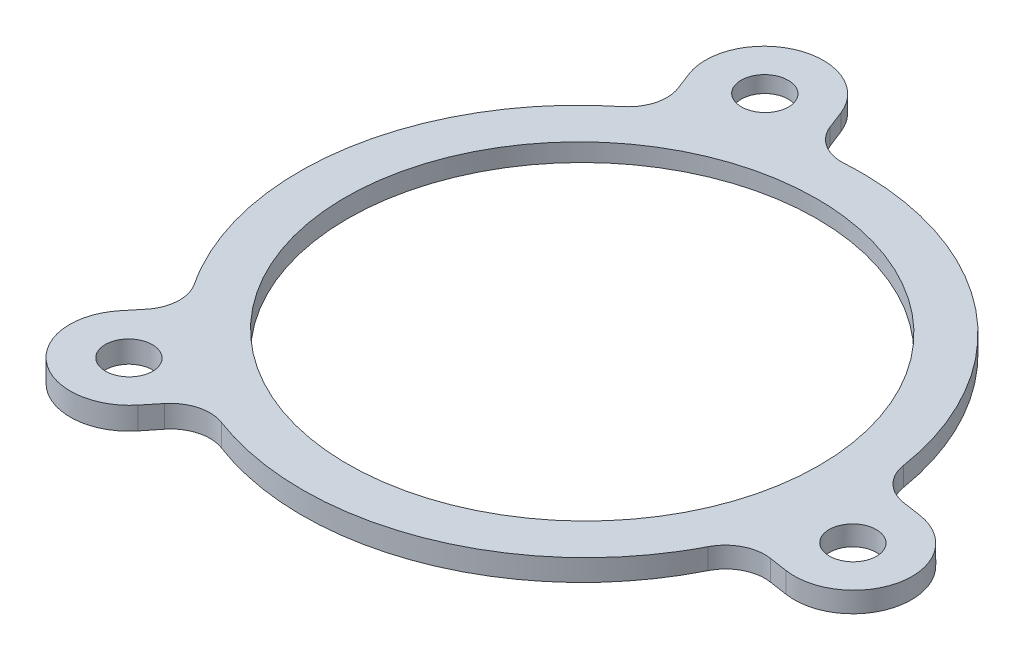
SolidWorks part; units mm, degrees
material "5454-O"
ref_plane "Front Plane" through (0, 0, 0) normal (0, 0, 1) x (1, 0, 0)
ref_plane "Top Plane" through (0, 0, 0) normal (0, 1, 0) x (1, 0, 0)
ref_plane "Right Plane" through (0, 0, 0) normal (1, 0, 0) x (0, 0, -1)
sketch "Sketch1" plane through (0, 0, 0) normal (0, 0, 1) x (1, 0, 0)
  line L0 (-3.7459, 1) -> (5.6477, 1) construction
  dimension "D1" = 1
ref_plane "Plane1" through (0, 0.9999, -0.0099) normal (0, 1, -0.0099) x (1, 0, 0)
sketch "Sketch2" plane through (0, 0, 0) normal (0, 1, 0) x (1, 0, 0)
  line L0 (0, 0) -> (-6.0205, 15.3624) construction
  line L1 (0, 0) -> (-10.294, -12.8951) construction
  line L2 (0, 0) -> (16.3145, -2.4673) construction
  line L3 (-6.0205, 15.3624) -> (-3.2273, 16.4571) construction
  line L4 (-6.0205, 15.3624) -> (-8.8136, 14.2678) construction
  line L5 (-3.2273, 16.4571) -> (-2.3151, 14.1294) construction
  line L6 (-8.8136, 14.2678) -> (-7.9014, 11.9402) construction
  line L7 (16.3145, -2.4673) -> (16.7631, 0.4989) construction
  line L8 (16.3145, -2.4673) -> (15.8659, -5.4336) construction
  line L9 (16.7631, 0.4989) -> (14.2912, 0.8728) construction
  line L10 (15.8659, -5.4336) -> (13.394, -5.0598) construction
  line L11 (-10.294, -12.8951) -> (-7.9495, -14.7667) construction
  line L12 (-10.294, -12.8951) -> (-12.6386, -11.0234) construction
  line L13 (-12.6386, -11.0234) -> (-11.0789, -9.0696) construction
  line L14 (-7.9495, -14.7667) -> (-6.3898, -12.8129) construction
  line L15 (-8.8136, 14.2678) -> (-8.4608, 13.3674)
  line L16 (-3.2273, 16.4571) -> (-2.8744, 15.5566)
  line L17 (16.7631, 0.4989) -> (15.8069, 0.6436)
  line L18 (15.8659, -5.4336) -> (14.9097, -5.289)
  line L19 (-7.9495, -14.7667) -> (-7.3461, -14.0109)
  line L20 (-12.6386, -11.0234) -> (-12.0352, -10.2676)
  arc A0 (-8.8136, 14.2678) -> (-3.2273, 16.4571) centre (-6.0205, 15.3624) cw
  arc A1 (16.7631, 0.4989) -> (15.8659, -5.4336) centre (16.3145, -2.4673) cw
  arc A2 (-7.9495, -14.7667) -> (-12.6386, -11.0234) centre (-10.294, -12.8951) cw
  arc A3 (-0.8882, 14.2902) -> (14.1319, 2.2998) centre (0, 0) cw
  arc A4 (12.8198, -6.3759) -> (-5.0743, -13.3885) centre (0, 0) cw
  arc A5 (-11.9316, -7.9144) -> (-9.0576, 11.0887) centre (0, 0) cw
  arc A6 (-11.9316, -7.9144) -> (-12.0352, -10.2676) centre (-13.5983, -9.0199) cw
  arc A7 (12.8198, -6.3759) -> (14.9097, -5.289) centre (14.6106, -7.2665) cw
  arc A8 (-0.8882, 14.2902) -> (-2.8744, 15.5566) centre (-1.0123, 16.2864) cw
  arc A9 (-7.3461, -14.0109) -> (-5.0743, -13.3885) centre (-5.7831, -15.2587) cw
  arc A10 (15.8069, 0.6436) -> (14.1319, 2.2998) centre (16.1059, 2.6211) cw
  arc A11 (-9.0576, 11.0887) -> (-8.4608, 13.3674) centre (-10.3229, 12.6376) ccw
  circle A12 centre (0, 0) radius 12
  circle A13 centre (-6.0205, 15.3624) radius 1.2
  circle A14 centre (16.3145, -2.4673) radius 1.2
  circle A15 centre (-10.294, -12.8951) radius 1.2
  dimension "D1" = 2
  dimension "D2" = 2
extrude "Boss-Extrude1" add sketch "Sketch2" along normal up to surface (0.8581 mm away) up to plane "Plane1"
sketch3d "3DSketch2"
  point P0 (20.3145, 1.4781, 16.8951)
